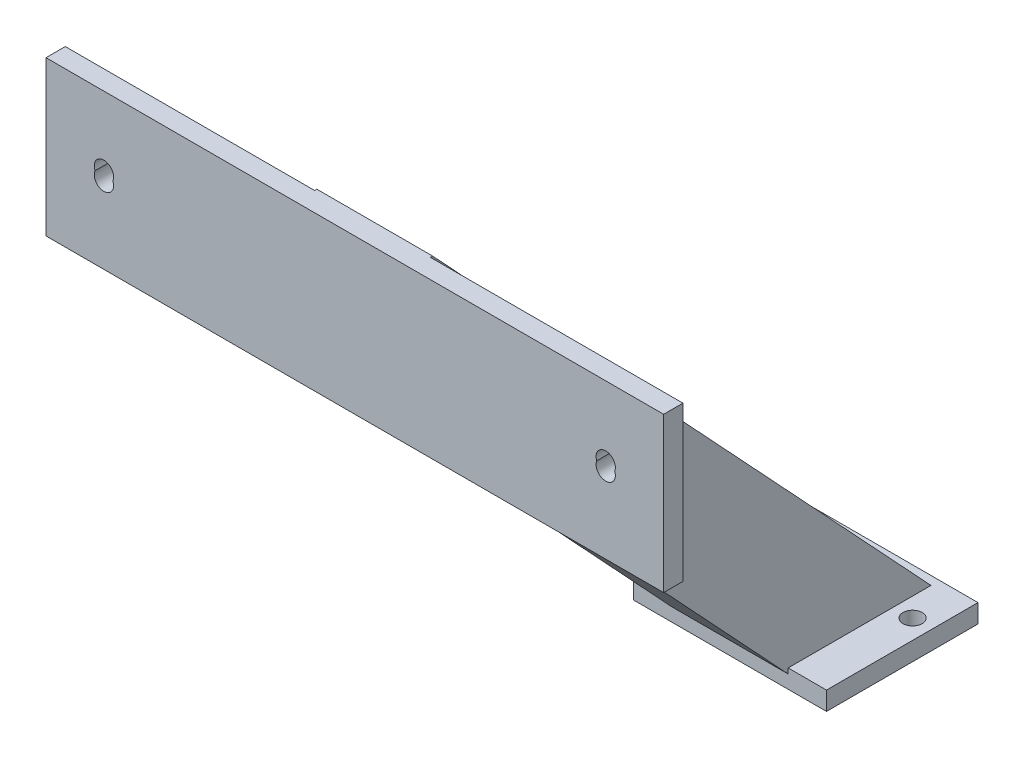
SolidWorks part; units mm, degrees
ref_plane "Front Plane" through (0, 0, 0) normal (0, 0, 1) x (1, 0, 0)
ref_plane "Top Plane" through (0, 0, 0) normal (0, 1, 0) x (1, 0, 0)
ref_plane "Right Plane" through (0, 0, 0) normal (1, 0, 0) x (0, 0, -1)
sketch "Sketch1" plane through (0, 0, 0) normal (0, 0, 1) x (1, 0, 0)
  line L1 (-79.5825, 25.9499) -> (80.4175, 25.9499)
  line L2 (-79.5825, 25.9499) -> (-79.5825, -14.0501)
  line L3 (-79.5825, -14.0501) -> (80.4175, -14.0501)
  line L4 (80.4175, 25.9499) -> (80.4175, -14.0501)
  line L5 (-79.5825, 25.9499) -> (80.4175, -14.0501) construction
  line L6 (-79.5825, -14.0501) -> (80.4175, 25.9499) construction
  point P0 (0.4175, 5.9499)
  dimension "D1" = 160
  dimension "D2" = 40
extrude "Boss-Extrude1" add sketch "Sketch1" along normal blind 5 contours L1 L4 L3 L2
sketch "Sketch6" plane through (0, 0, 0) normal (1, 0, 0) x (0, 0, -1)
  line L0 (0, 6.0443) -> (28.5274, -24.5476) construction
  line L1 (0, 25.9499) -> (0, -14.0501) construction
  dimension "D1" = 43
ref_plane "Plane2" through (0, 2.8113, -3.0148) normal (0, 0.682, -0.7314) x (0, -0.7314, -0.682)
sketch "Sketch10" plane through (0, 2.8113, -3.0148) normal (0, 0.682, -0.7314) x (0, -0.7314, -0.682)
  line L0 (-4.4205, 0) -> (37.4087, 0) construction
  line L1 (-23.5489, 15) -> (174.5311, 15)
  line L2 (-23.5489, 15) -> (-23.5489, -15)
  line L3 (-23.5489, -15) -> (174.5311, -15)
  line L4 (174.5311, 15) -> (174.5311, -15)
  line L5 (-23.5489, 15) -> (174.5311, -15) construction
  line L6 (-23.5489, -15) -> (174.5311, 15) construction
  point P0 (75.4911, 0)
  dimension "D1" = 30
extrude "Boss-Extrude3" add sketch "Sketch10" along normal mid plane 28
sketch "Sketch12" plane through (-15, 0, 0) normal (-1, 0, 0) x (0, 0, 1)
  line L0 (5, -9.1218) -> (20.7054, 7.7203)
  line L1 (5, -9.1218) -> (23.2845, 10.486) construction
  line L2 (5, 25.9499) -> (5, -14.0501) construction
  line L3 (20.7054, 7.7203) -> (2.8066, 29.5819)
  line L4 (-132.2836, -115.2846) -> (2.8066, 29.5819) construction
  line L5 (2.8066, 29.5819) -> (23.2845, 10.486) construction
  line L6 (2.8066, 29.5819) -> (-0.5803, 25.9499)
  line L7 (5, 25.9499) -> (0, 25.9499) construction
  line L8 (-0.5803, 25.9499) -> (5, 25.9499)
  line L9 (5, 25.9499) -> (0, 25.9499) construction
  line L10 (5, 25.9499) -> (5, -9.1218)
  line L11 (5, -9.1218) -> (5, 25.9499) construction
extrude "Cut-Extrude1" cut sketch "Sketch12" against normal blind 30
sketch "Sketch13" plane through (0, 17.2226, 16.0603) normal (0, 0.7314, 0.682) x (1, 0, 0)
  line L0 (30.7801, 4.1222) -> (-30.7801, 4.1222) construction
  line L1 (-15.8457, 19.6512) -> (16.2044, 19.6512)
  line L2 (-15.8457, 19.6512) -> (-15.8457, -11.4067)
  line L3 (-15.8457, -11.4067) -> (16.2044, -11.4067)
  line L4 (16.2044, 19.6512) -> (16.2044, -11.4067)
  line L5 (-15.8457, 19.6512) -> (16.2044, -11.4067) construction
  line L6 (-15.8457, -11.4067) -> (16.2044, 19.6512) construction
  point P0 (0.1794, 4.1222)
sketch "Sketch17" plane through (15, 0, 0) normal (1, 0, 0) x (0, 0, -1)
  line L0 (-24.2073, 10.9859) -> (-20.5615, 7.3009)
  line L1 (-20.5615, 7.3009) -> (-0.9369, 30.8646)
  line L2 (-0.9369, 30.8646) -> (-24.2073, 10.9859)
extrude "Cut-Extrude4" cut sketch "Sketch17" against normal through all
sketch "Sketch18" plane through (0, 0, 0) normal (0, 0, -1) x (-1, 0, 0)
  line L0 (-80.4175, 25.9499) -> (-80.4175, -14.0501) construction
  circle A0 centre (-65.4175, 7.7383) radius 2.5
  circle A1 centre (64.5825, 7.9695) radius 2.5
  dimension "D1" = 5
  dimension "D2" = 5
  dimension "D3" = 130
  dimension "D4" = 15
extrude "Cut-Extrude5" cut sketch "Sketch18" against normal through all
sketch "Sketch19" plane through (15, 0, 0) normal (1, 0, 0) x (0, 0, -1)
  line L0 (132.631, -114.9038) -> (93.6433, -114.9038)
  line L1 (-0.4043, -14.0501) -> (111.8057, -134.3806) construction
  line L2 (93.6433, -114.9038) -> (93.6433, -140.2598)
  line L3 (93.6433, -140.2598) -> (133.2062, -140.2598)
  line L4 (133.2062, -140.2598) -> (133.2062, -115.1728)
  line L5 (133.2062, -115.1728) -> (132.631, -114.9038)
extrude "Cut-Extrude6" cut sketch "Sketch19" against normal through all
sketch "Sketch20" plane through (0, -114.9038, 0) normal (0, -1, 0) x (1, 0, 0)
  line L1 (-25.0683, -92.6752) -> (24.9317, -92.6752)
  line L2 (-25.0683, -92.6752) -> (-25.0683, -131.9272)
  line L3 (-25.0683, -131.9272) -> (24.9317, -131.9272)
  line L4 (24.9317, -92.6752) -> (24.9317, -131.9272)
  line L5 (-25.0683, -92.6752) -> (24.9317, -131.9272) construction
  line L6 (-25.0683, -131.9272) -> (24.9317, -92.6752) construction
  point P0 (-0.0683, -112.3012)
  dimension "D1" = 50
extrude "Boss-Extrude4" add sketch "Sketch20" along normal mid plane 4.8
sketch "Sketch21" plane through (0, -112.5038, 0) normal (0, 1, 0) x (1, 0, 0)
  line L0 (-25.0683, 92.6752) -> (-25.0683, 131.9272) construction
  circle A0 centre (19.9317, 119.9781) radius 2.5
  circle A1 centre (-20.0683, 119.9073) radius 2.5
  dimension "D1" = 5
  dimension "D2" = 5
  dimension "D3" = 40
  dimension "D4" = 5
extrude "Cut-Extrude7" cut sketch "Sketch21" against normal through all
sketch "Sketch22" plane through (0, 17.2226, 16.0603) normal (0, 0.7314, 0.682) x (1, 0, 0)
  line L5 (-14.9923, 19.3524) -> (16.7257, 19.3524)
  line L6 (-14.9923, 19.3524) -> (-14.9923, 11.923)
  line L7 (-14.9923, 11.923) -> (16.7257, 11.923)
  line L8 (16.7257, 19.3524) -> (16.7257, 11.923)
  line L9 (-14.9923, 19.3524) -> (16.7257, 11.923) construction
  line L10 (-14.9923, 11.923) -> (16.7257, 19.3524) construction
  point P0 (0.8667, 15.6377)
extrude "Cut-Extrude9" cut sketch "Sketch22" along normal blind 1 and the other way blind 1
sketch "Sketch23" plane through (-15, 0, 0) normal (-1, 0, 0) x (0, 0, 1)
  line L0 (2.0816, 29.4075) -> (7.1912, 25.3401)
  line L1 (7.1912, 25.3401) -> (3.6577, 30.3735)
  line L2 (3.6577, 30.3735) -> (2.0816, 29.4075)
extrude "Cut-Extrude10" cut sketch "Sketch23" against normal blind 1
sketch "Sketch15" plane through (0, 0, 5) normal (0, 0, 1) x (1, 0, 0)
  line L0 (-79.5825, 25.9499) -> (80.4175, 25.9499) construction
  line L1 (-79.5825, -14.0501) -> (80.4175, -14.0501) construction
  line L2 (-79.5825, 25.9499) -> (-79.5825, -14.0501) construction
  circle A0 centre (65.4175, 5.9499) radius 2.5
  circle A1 centre (-64.5825, 5.9499) radius 2.5
  dimension "D1" = 5
  dimension "D2" = 5
  dimension "D3" = 20
  dimension "D4" = 20
  dimension "D5" = 130
  dimension "D6" = 15
extrude "Cut-Extrude3" cut sketch "Sketch15" against normal through all
